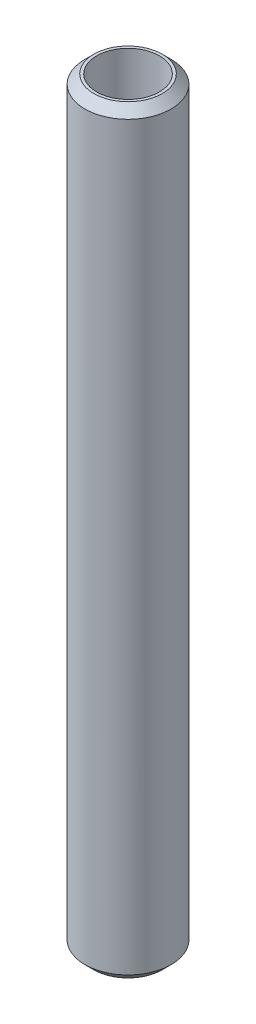
SolidWorks part; units mm, degrees
ref_plane "Front Plane" through (0, 0, 0) normal (0, 0, 1) x (1, 0, 0)
ref_plane "Top Plane" through (0, 0, 0) normal (0, 1, 0) x (1, 0, 0)
ref_plane "Right Plane" through (0, 0, 0) normal (1, 0, 0) x (0, 0, -1)
sketch "Sketch1" plane through (0, 0, 0) normal (0, 1, 0) x (1, 0, 0)
  circle A0 centre (0, 0) radius 22.5
  dimension "SHAFT_OD" = 45
extrude "Boss-Extrude1" add sketch "Sketch1" along normal blind 396.2797
sketch "Sketch2" plane through (0, 0, 0) normal (0, 1, 0) x (1, 0, 0)
  circle A0 centre (0, 0) radius 16.3802
  dimension "BORE_D" = 32.7605
extrude "Cut-Extrude1" cut sketch "Sketch2" along normal through all
chamfer "Chamfer1" distance 4.6606 angle 45 2 edges at (0, 396.2797, 22.5) (0, 0, 22.5)
